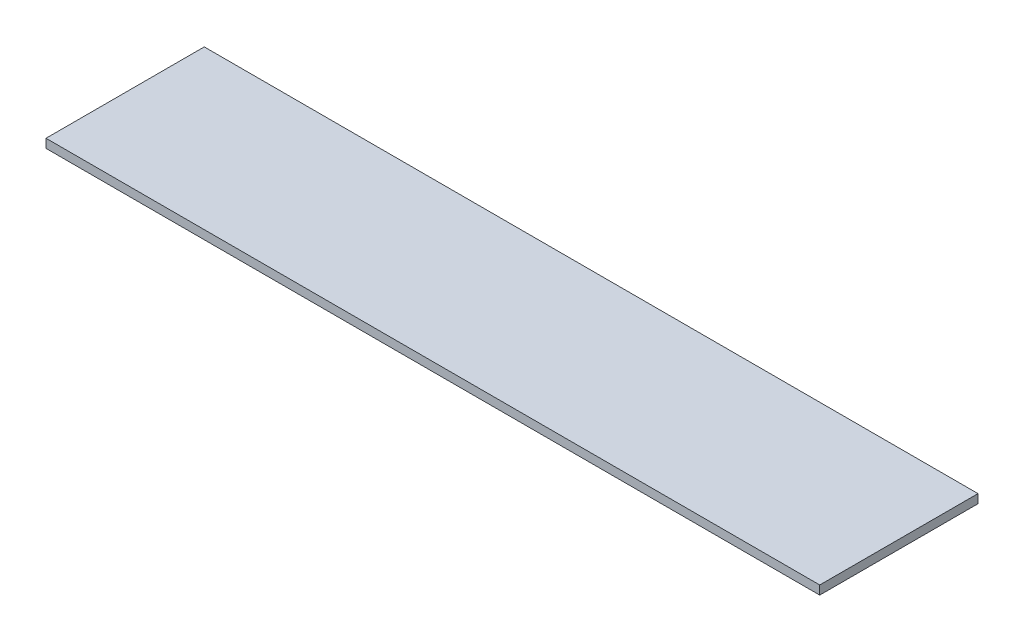
SolidWorks part; units mm, degrees
ref_plane "Alzado" through (0, 0, 0) normal (0, 0, 1) x (1, 0, 0)
ref_plane "Planta" through (0, 0, 0) normal (0, 1, 0) x (1, 0, 0)
ref_plane "Vista lateral" through (0, 0, 0) normal (1, 0, 0) x (0, 0, -1)
sketch "Sketch1" plane through (0, 0, 0) normal (0, 1, 0) x (1, 0, 0)
  line L1 (0.0164, -1.7) -> (88.0164, -1.7)
  line L2 (0.0164, -1.7) -> (0.0164, 16.3)
  line L3 (0.0164, 16.3) -> (88.0164, 16.3)
  line L4 (88.0164, -1.7) -> (88.0164, 16.3)
  line L5 (0.0164, -1.7) -> (88.0164, 16.3) construction
  line L6 (0.0164, 16.3) -> (88.0164, -1.7) construction
  point P4 (44, 8.15)
  dimension "D1" = 88
  dimension "D2" = 18
extrude "Boss-Extrude1" add sketch "Sketch1" along normal blind 1
